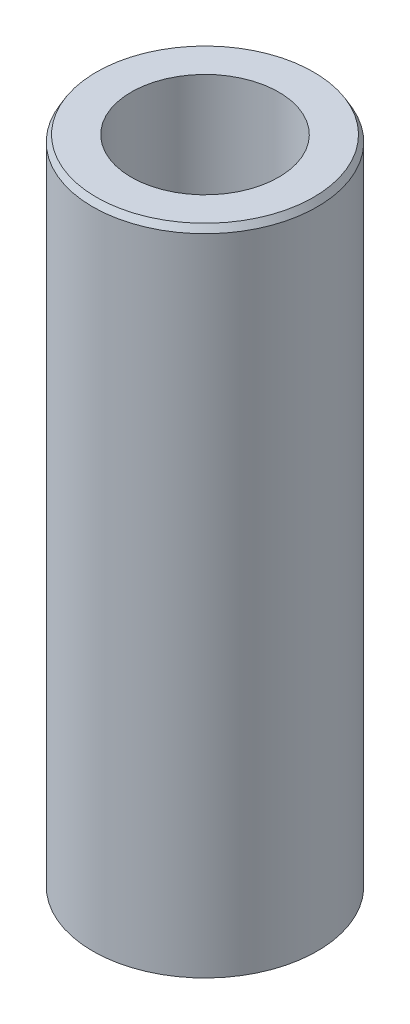
SolidWorks part; units mm, degrees
ref_plane "Front Plane" through (0, 0, 0) normal (0, 0, 1) x (1, 0, 0)
ref_plane "Top Plane" through (0, 0, 0) normal (0, 1, 0) x (1, 0, 0)
ref_plane "Right Plane" through (0, 0, 0) normal (1, 0, 0) x (0, 0, -1)
sketch "Sketch1" plane through (0, 0, 0) normal (0, 1, 0) x (1, 0, 0)
  circle A0 centre (0, 0) radius 10
  dimension "SHAFT_OD" = 20
extrude "Boss-Extrude1" add sketch "Sketch1" along normal blind 58.3154
sketch "Sketch2" plane through (0, 0, 0) normal (0, 1, 0) x (1, 0, 0)
  circle A0 centre (0, 0) radius 6.5709
  dimension "BORE_D" = 13.1418
extrude "Cut-Extrude1" cut sketch "Sketch2" along normal through all
chamfer "Chamfer1" distance 0.5735 angle 30 2 edges at (0, 58.3154, 10) (0, 0, 10) first distance on face at (0, 58.3154, 10) first distance on face at (0, 0, 6.5709)
